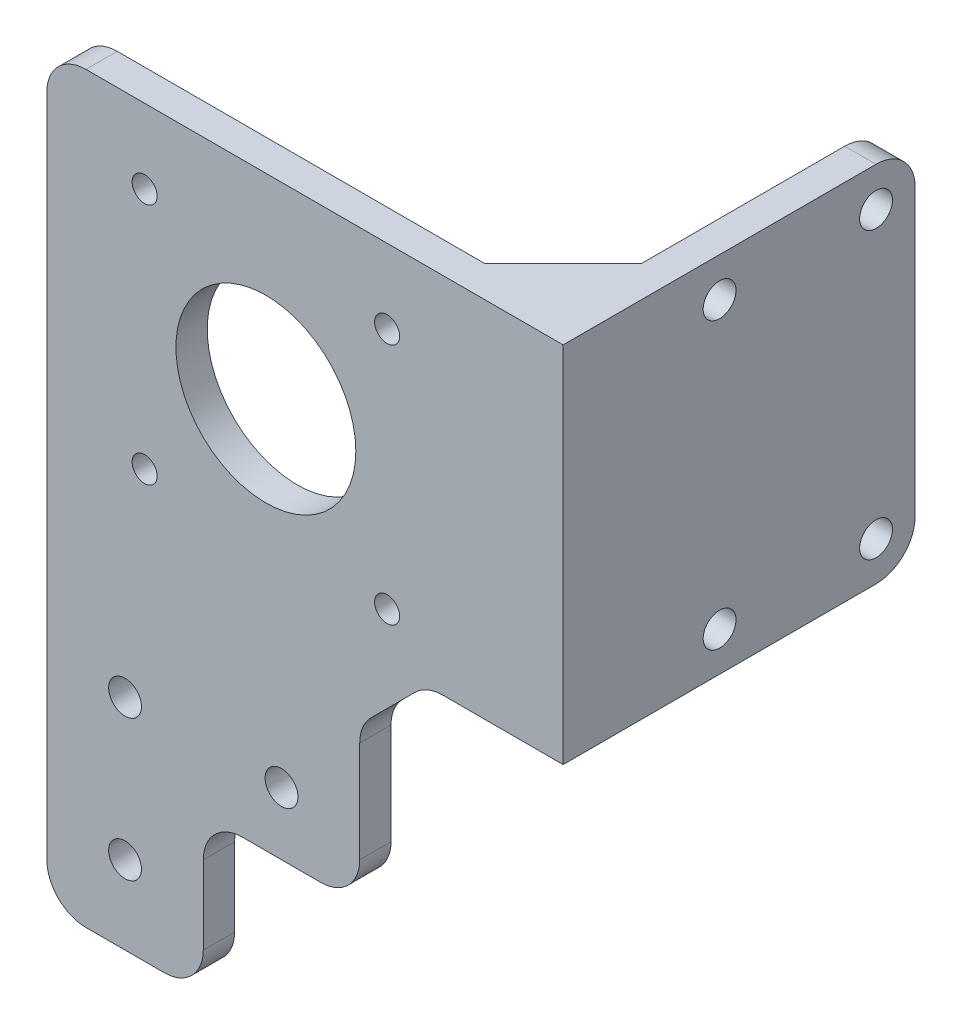
SolidWorks part; units mm, degrees
ref_plane "Спереди" through (0, 0, 0) normal (0, 0, 1) x (1, 0, 0)
ref_plane "Сверху" through (0, 0, 0) normal (0, 1, 0) x (1, 0, 0)
ref_plane "Справа" through (0, 0, 0) normal (1, 0, 0) x (0, 0, -1)
sketch "Model" plane through (0, 0, 0) normal (0, 0, 1) x (1, 0, 0)
  line L69 (274.0282, 189.1642) -> (274.0282, 151.2354)
  line L70 (272.5637, 147.6998) -> (265.4927, 140.6288)
  line L71 (264.0282, 137.0932) -> (264.0282, 124.1643)
  line L72 (259.0282, 119.1644) -> (249.0282, 119.1644)
  line L73 (244.0283, 114.1644) -> (244.0283, 104.1644)
  line L74 (239.0283, 99.1644) -> (229.0283, 99.1644)
  line L75 (224.0283, 104.1644) -> (224.0283, 189.1642)
  line L76 (229.0283, 194.1642) -> (269.0282, 194.1642)
  circle A41 centre (267.5282, 184.6642) radius 1.6
  circle A42 centre (267.5282, 153.6643) radius 1.6
  circle A43 centre (236.5283, 153.6643) radius 1.6
  circle A44 centre (236.5283, 184.6642) radius 1.6
  circle A45 centre (254.0282, 127.1643) radius 2.1
  circle A46 centre (234.0283, 127.1643) radius 2.1
  circle A47 centre (234.0283, 109.1644) radius 2.1
  circle A48 centre (252.0282, 169.1643) radius 11.5
  arc A150 (272.5637, 147.6998) -> (274.0282, 151.2354) centre (269.0282, 151.2354) ccw
  arc A151 (265.4927, 140.6288) -> (264.0282, 137.0932) centre (269.0282, 137.0932) ccw
  arc A152 (259.0282, 119.1644) -> (264.0282, 124.1643) centre (259.0282, 124.1643) ccw
  arc A153 (249.0282, 119.1644) -> (244.0283, 114.1644) centre (249.0282, 114.1644) ccw
  arc A154 (239.0283, 99.1644) -> (244.0283, 104.1644) centre (239.0283, 104.1644) ccw
  arc A155 (224.0283, 104.1644) -> (229.0283, 99.1644) centre (229.0283, 104.1644) ccw
  arc A156 (229.0283, 194.1642) -> (224.0283, 189.1642) centre (229.0283, 189.1642) ccw
  arc A157 (274.0282, 189.1642) -> (269.0282, 194.1642) centre (269.0282, 189.1642) ccw
  dimension "D1" = 5
extrude "Бобышка-Вытянуть1" add sketch "Model" along normal blind 4
sketch "Эскиз1" plane through (0, 0, 0) normal (0, 0, -1) x (-1, 0, 0)
  line L0 (-269.0282, 194.1642) -> (-274.0282, 194.1642) construction
  line L1 (-274.0282, 194.1642) -> (-274.0282, 147.6998) construction
  line L2 (-274.0282, 147.6998) -> (-272.5637, 147.6998) construction
  line L4 (-274.0282, 194.1642) -> (-286.0282, 194.1642)
  line L5 (-274.0282, 189.1642) -> (-274.0282, 152.0643)
  line L6 (-274.0282, 147.6998) -> (-286.0282, 147.6998)
  line L7 (-286.0282, 194.1642) -> (-286.0282, 147.6998)
  line L8 (-274.0282, 194.1642) -> (-269.0282, 194.1642)
  line L10 (-274.0282, 189.1642) -> (-269.0282, 189.1642)
  line L11 (-269.0282, 194.1642) -> (-269.0282, 189.1642)
  line L12 (-274.0282, 147.6998) -> (-271.5282, 147.6998)
  line L14 (-274.0282, 152.0643) -> (-271.5282, 152.0643)
  line L15 (-271.5282, 147.6998) -> (-271.5282, 152.0643)
  dimension "D1" = 12
extrude "Бобышка-Вытянуть2" add sketch "Эскиз1" against normal blind 4
fillet "Скругление1" radius 5 1 edges at (272.5637, 147.6998, 2)
sketch "Эскиз2" plane through (286.0282, 0, 0) normal (1, 0, 0) x (0, 0, -1)
  line L6 (-4, 194.1642) -> (36, 194.1642)
  line L7 (-4, 194.1642) -> (-4, 147.6998)
  line L8 (-4, 147.6998) -> (36, 147.6998)
  line L9 (41, 189.1642) -> (41, 152.6998)
  arc A6 (41, 152.6998) -> (36, 147.6998) centre (36, 152.6998) cw
  arc A7 (41, 189.1642) -> (36, 194.1642) centre (36, 189.1642) ccw
  circle A8 centre (36, 189.1642) radius 2.1
  circle A9 centre (36, 152.6998) radius 2.1
  circle A10 centre (16, 189.1642) radius 2.1
  circle A11 centre (16, 152.6998) radius 2.1
  point P27 (41, 194.1642)
  dimension "D6" = 5
  dimension "D7" = 4.2
  dimension "D8" = 4.2
  dimension "D1" = 45
  dimension "D9" = 2
extrude "Бобышка-Вытянуть3" add sketch "Эскиз2" along normal blind 4
sketch "Эскиз3" plane through (0, 194.1642, 0) normal (0, 1, 0) x (1, 0, 0)
  line L5 (286.0282, 0) -> (286.0282, 10)
  line L6 (286.0282, 10) -> (276.0282, 0)
  line L7 (286.0282, 0) -> (229.0283, 0) construction
  line L8 (276.0282, 0) -> (286.0282, 0)
  dimension "D3" = 10
  dimension "D4" = 10
extrude "Бобышка-Вытянуть4" add sketch "Эскиз3" against normal blind 4
ref_plane "Плоскость1" through (0, 170.932, 0) normal (0, 1, 0) x (1, 0, 0)
mirror "Зеркальное отражение1" about plane through (0, 170.932, 0) normal (0, 1, 0) of "Бобышка-Вытянуть4"
